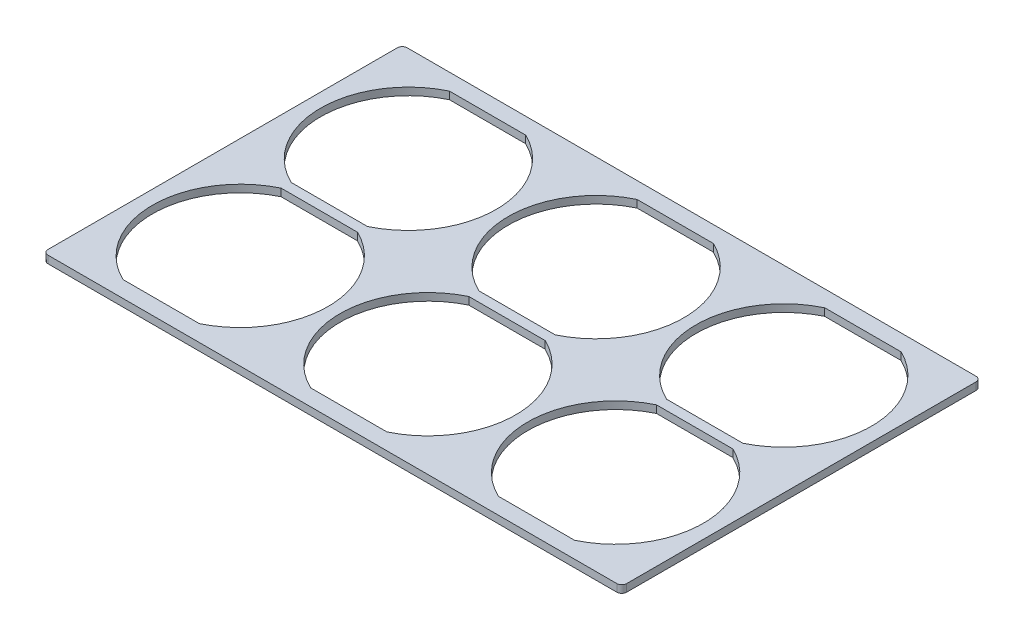
SolidWorks part; units mm, degrees
material "NEOPRENE"
ref_plane "Front" through (0, 0, 0) normal (0, 0, 1) x (1, 0, 0)
ref_plane "Top" through (0, 0, 0) normal (0, 1, 0) x (1, 0, 0)
ref_plane "Right" through (0, 0, 0) normal (1, 0, 0) x (0, 0, -1)
sketch "Sketch1" plane through (0, 0, 0) normal (0, 1, 0) x (1, 0, 0)
  line L0 (-24.3078, -3.1623) -> (24.3078, -3.1623)
  line L1 (-180.975, 114.3) -> (180.975, 114.3)
  line L2 (-184.15, 111.125) -> (-184.15, -111.125)
  line L3 (-180.975, -114.3) -> (180.975, -114.3)
  line L4 (184.15, 111.125) -> (184.15, -111.125)
  line L5 (-184.15, 114.3) -> (184.15, -114.3) construction
  line L6 (-184.15, -114.3) -> (184.15, 114.3) construction
  line L7 (95.1365, -3.1623) -> (143.7521, -3.1623)
  line L8 (95.1365, -3.1623) -> (95.1365, -103.8733) construction
  line L9 (95.1365, -103.8733) -> (143.7521, -103.8733)
  line L10 (143.7521, -3.1623) -> (143.7521, -103.8733) construction
  line L11 (95.1365, -3.1623) -> (143.7521, -103.8733) construction
  line L12 (95.1365, -103.8733) -> (143.7521, -3.1623) construction
  line L13 (-24.3078, -103.8733) -> (24.3078, -103.8733)
  line L14 (-143.7521, -3.1623) -> (-95.1365, -3.1623)
  line L15 (-143.7521, -103.8733) -> (-95.1365, -103.8733)
  line L16 (-24.3078, 103.8733) -> (24.3078, 103.8733)
  line L17 (-24.3078, 3.1623) -> (24.3078, 3.1623)
  line L18 (-143.7521, 103.8733) -> (-95.1365, 103.8733)
  line L19 (-143.7521, 3.1623) -> (-95.1365, 3.1623)
  line L20 (95.1365, 103.8733) -> (143.7521, 103.8733)
  line L21 (95.1365, 3.1623) -> (143.7521, 3.1623)
  line L22 (-95.1365, -103.8733) -> (-24.3078, -103.8733) construction
  line L23 (24.3078, -103.8733) -> (95.1365, -103.8733) construction
  line L24 (119.5086, 53.5178) -> (119.5086, -53.5178) construction
  line L25 (24.3078, 3.1623) -> (24.3078, -3.1623) construction
  line L26 (-175.3235, -53.5178) -> (-184.15, -53.5178) construction
  line L27 (175.3235, -53.5178) -> (184.15, -53.5178) construction
  line L28 (-24.3078, -103.8733) -> (-24.3078, -114.3) construction
  line L29 (-24.3078, 103.8733) -> (-24.3078, 114.3) construction
  arc A0 (95.1365, -3.1623) -> (95.1365, -103.8733) centre (119.5086, -53.5178) ccw
  arc A1 (143.7521, -3.1623) -> (143.7521, -103.8733) centre (119.38, -53.5178) cw
  arc A2 (-184.15, -111.125) -> (-180.975, -114.3) centre (-180.975, -111.125) ccw
  arc A3 (184.15, -111.125) -> (180.975, -114.3) centre (180.975, -111.125) cw
  arc A4 (184.15, 111.125) -> (180.975, 114.3) centre (180.975, 111.125) ccw
  arc A5 (-180.975, 114.3) -> (-184.15, 111.125) centre (-180.975, 111.125) ccw
  circle A6 centre (119.38, 53.5178) radius 25.4 construction
  circle A7 centre (119.38, 53.5178) radius 25.4 construction
  circle A8 centre (0, 53.5178) radius 25.4 construction
  circle A9 centre (0, 53.5178) radius 25.4 construction
  arc A10 (-24.3078, -3.1623) -> (-24.3078, -103.8733) centre (0.0643, -53.5178) ccw
  arc A11 (24.3078, -3.1623) -> (24.3078, -103.8733) centre (-0.0643, -53.5178) cw
  arc A12 (-143.7521, -3.1623) -> (-143.7521, -103.8733) centre (-119.38, -53.5178) ccw
  arc A13 (-95.1365, -3.1623) -> (-95.1365, -103.8733) centre (-119.5086, -53.5178) cw
  arc A14 (-24.3078, 103.8733) -> (-24.3078, 3.1623) centre (0.0643, 53.5178) ccw
  arc A15 (24.3078, 103.8733) -> (24.3078, 3.1623) centre (-0.0643, 53.5178) cw
  arc A16 (-143.7521, 103.8733) -> (-143.7521, 3.1623) centre (-119.38, 53.5178) ccw
  arc A17 (-95.1365, 103.8733) -> (-95.1365, 3.1623) centre (-119.5086, 53.5178) cw
  arc A18 (95.1365, 103.8733) -> (95.1365, 3.1623) centre (119.5086, 53.5178) ccw
  arc A19 (143.7521, 103.8733) -> (143.7521, 3.1623) centre (119.38, 53.5178) cw
  circle A20 centre (-119.38, 53.5178) radius 25.4 construction
  point P0 (0, 0)
  point P6 (119.4443, -53.5178)
  dimension "D4" = 111.887
  dimension "D8" = 3.175
  dimension "D1" = 368.3
  dimension "D2" = 228.6
  dimension "D3" = 100.711
  dimension "D5" = 48.6156
  dimension "D11" = 3
  dimension "D12" = 2
extrude "Boss-Extrude1" add sketch "Sketch1" along normal blind 4.7752
